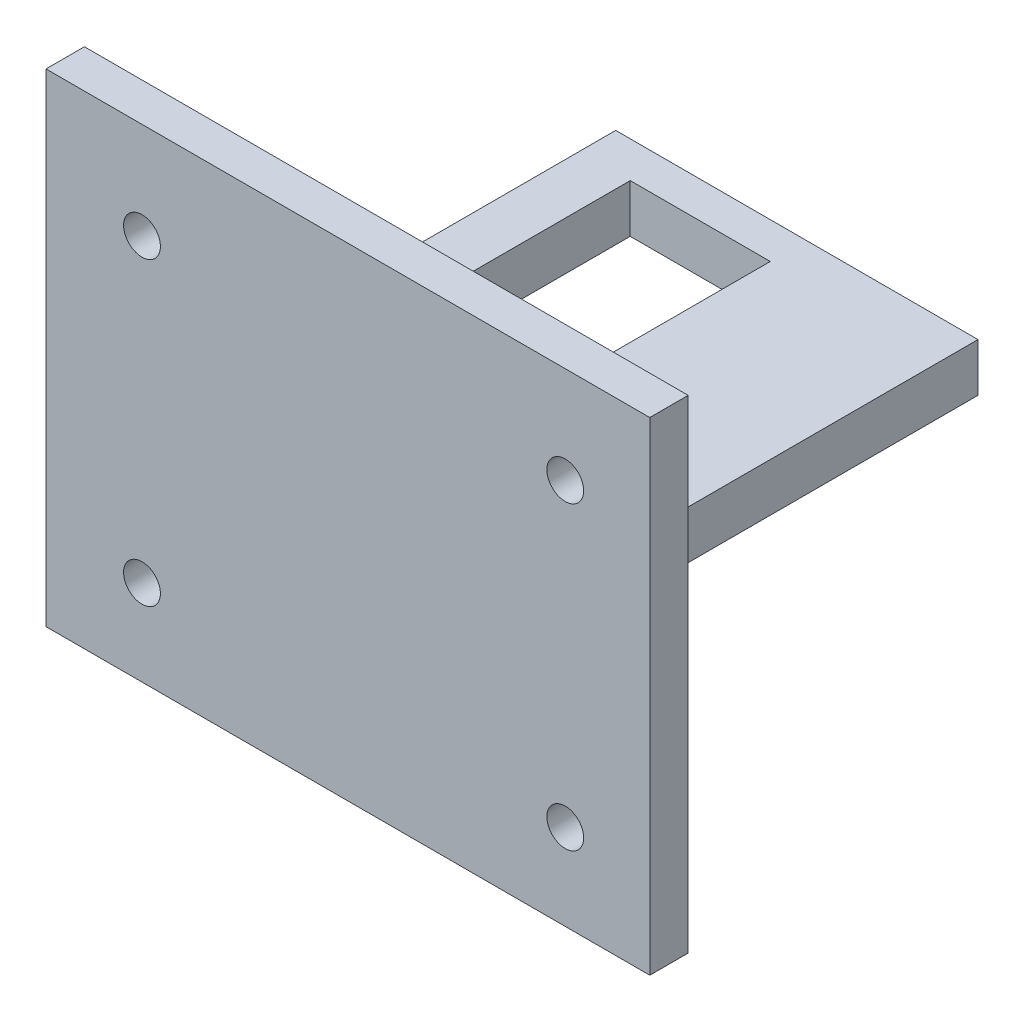
SolidWorks part; units mm, degrees
ref_plane "Front Plane" through (0, 0, 0) normal (0, 0, 1) x (1, 0, 0)
ref_plane "Top Plane" through (0, 0, 0) normal (0, 1, 0) x (1, 0, 0)
ref_plane "Right Plane" through (0, 0, 0) normal (1, 0, 0) x (0, 0, -1)
sketch "Sketch1" plane through (0, 0, 0) normal (0, 0, 1) x (1, 0, 0)
  line L1 (25, -20) -> (-25, -20)
  line L2 (25, -20) -> (25, 20)
  line L3 (25, 20) -> (-25, 20)
  line L4 (-25, -20) -> (-25, 20)
  line L5 (25, -20) -> (-25, 20) construction
  line L6 (25, 20) -> (-25, -20) construction
  point P0 (0, 0)
  dimension "D1" = 50
  dimension "D2" = 40
extrude "Boss-Extrude1" add sketch "Sketch1" along normal blind 3.18
sketch "Sketch4" plane through (0, 0, 0) normal (0, 0, -1) x (-1, 0, 0)
  line L1 (-15, 2) -> (15, 2)
  line L2 (-15, 2) -> (-15, -2)
  line L3 (-15, -2) -> (15, -2)
  line L4 (15, 2) -> (15, -2)
  line L5 (-15, 2) -> (15, -2) construction
  line L6 (-15, -2) -> (15, 2) construction
  point P0 (0, 0)
  dimension "D1" = 30
  dimension "D2" = 4
extrude "Boss-Extrude2" add sketch "Sketch4" along normal blind 36
sketch "Sketch8" plane through (0, 2, 0) normal (0, 1, 0) x (1, 0, 0)
  line L1 (-10.8, 31) -> (0.8, 31)
  line L2 (-10.8, 31) -> (-10.8, 8.9)
  line L3 (-10.8, 8.9) -> (0.8, 8.9)
  line L4 (0.8, 31) -> (0.8, 8.9)
  line L5 (-10.8, 31) -> (0.8, 8.9) construction
  line L6 (-10.8, 8.9) -> (0.8, 31) construction
  line L7 (-15, 36) -> (15, 36) construction
  line L8 (-5, 19.95) -> (0.8, 19.95) construction
  line L9 (15, 36) -> (15, 0) construction
  circle A0 centre (-5, 33.575) radius 1
  circle A1 centre (-5, 6.325) radius 1
  point P0 (-5, 19.95)
  point P7 (0, 0)
  point P13 (0, 0)
  point P14 (0, 0)
  dimension "D6" = 2
  dimension "D10" = 20
  dimension "D3" = 27.25
  dimension "D1" = 11.6
  dimension "D2" = 22.1
  dimension "D4" = 5
extrude "Cut-Extrude1" cut sketch "Sketch8" against normal through all both and the other way through all contours L4 L1 L2 L3 | A1 region at (-5, 2, -19.95)
sketch "Sketch9" plane through (0, 0, 0) normal (0, 0, -1) x (-1, 0, 0)
  line L0 (-18, 12) -> (17.0502, 12) construction
  line L1 (-18, -12.89) -> (17.05, -12.89) construction
  line L2 (17.0502, 12) -> (17.05, -12.89) construction
  line L3 (-18, 12) -> (-18, -12.89) construction
  circle A0 centre (-18, 12) radius 1.525
  circle A1 centre (17.0502, 12) radius 1.525
  circle A2 centre (17.05, -12.89) radius 1.525
  circle A3 centre (-18, -12.89) radius 1.525
  dimension "D1" = 3.05
  dimension "D2" = 35.05
  dimension "D3" = 24.89
  dimension "D4" = 12
  dimension "D5" = 18
  dimension "D6" = 35.0502
extrude "Cut-Extrude2" cut sketch "Sketch9" against normal through all
sketch "Sketch11" [suppressed] plane through (0, 0, 0) normal (1, 0, 0) x (0, 0, -1)
  line L0 (0, 20) -> (15.0901, 4.9099) construction
  line L1 (0, 20) -> (0, -20) construction
  dimension "D1" = 45
sketch "Sketch10" plane through (0, 0, 0) normal (0, 0, -1) x (-1, 0, 0)
  line L0 (15, 2) -> (-15, 2) construction
  line L1 (-2.5, 2) -> (2.5, 2)
  line L2 (-2.5, 2) -> (-2.5, 12)
  line L3 (-2.5, 12) -> (2.5, 12)
  line L4 (2.5, 2) -> (2.5, 12)
  line L5 (0, -0.4193) -> (0, 12.4193) construction
  point P10 (0, 6)
  dimension "D1" = 10
  dimension "5" = 5
extrude "Boss-Extrude3" [suppressed] add sketch "Sketch10" along direction (0, -0.7071, -0.7071) on the side of the normal up to surface
fillet "Fillet3" [suppressed] radius 2
fillet "Fillet4" radius 3 1 edges at (0, -2, 0)
sketch "Sketch12" plane through (0, -2, 0) normal (0, -1, 0) x (1, 0, 0)
  line L0 (-15, -36) -> (-15, -3) construction
  line L1 (15, -36) -> (-15, -36)
  line L2 (15, -36) -> (15, -34)
  line L3 (15, -34) -> (-15, -34)
  line L4 (-15, -36) -> (-15, -34)
  dimension "D1" = 2
extrude "Cut-Extrude3" cut sketch "Sketch12" against normal through all
